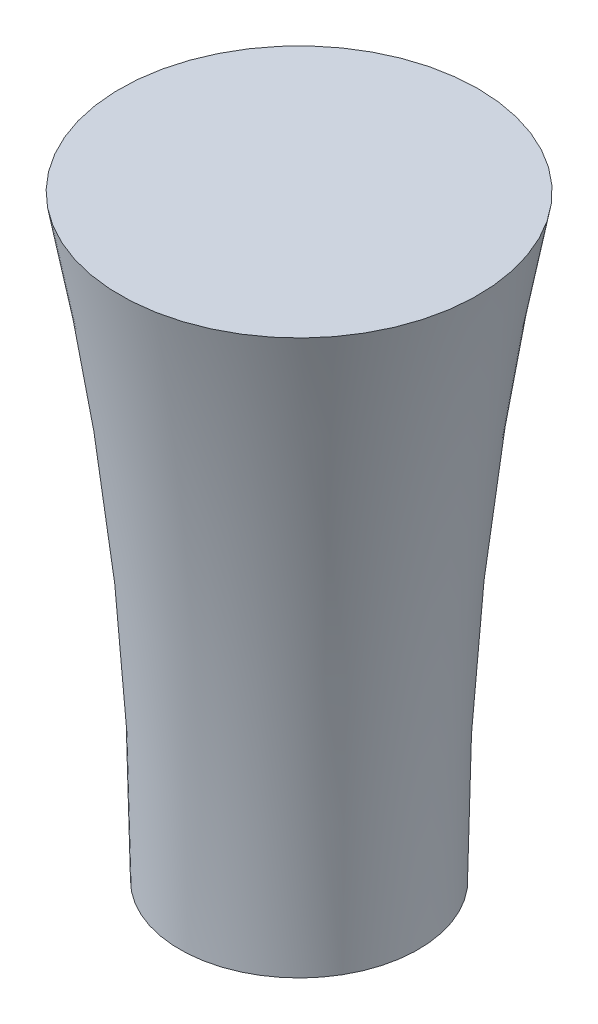
SolidWorks part; units mm, degrees
ref_plane "Front Plane" through (0, 0, 0) normal (0, 0, 1) x (1, 0, 0)
ref_plane "Top Plane" through (0, 0, 0) normal (0, 1, 0) x (1, 0, 0)
ref_plane "Right Plane" through (0, 0, 0) normal (1, 0, 0) x (0, 0, -1)
sketch "Sketch4" plane through (0, 0, 0) normal (0, 0, 1) x (1, 0, 0)
  line L0 (0, 0) -> (0, 5)
  line L1 (0, 5) -> (1.5, 5)
  line L2 (0, 0) -> (1, 0)
  line L3 (1, 0) -> (1, 4.1966) construction
  arc A0 (1, 0) -> (1.5, 5) centre (26.25, 0) cw
  dimension "D1" = 1
  dimension "D2" = 5
  dimension "D3" = 1.5
revolve "Revolve1" add sketch "Sketch4" angle 360 about L0
ref_axis "Axis1" through (0, 0, 0) along (0, 1, 0)
